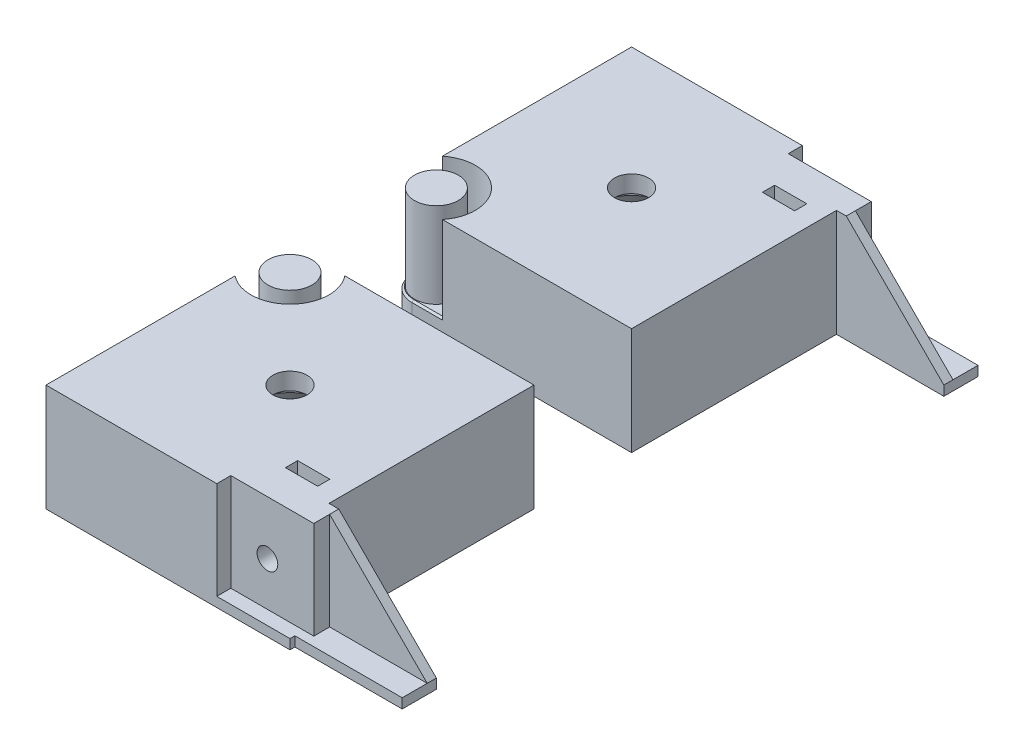
SolidWorks part; units mm, degrees
ref_plane "Front Plane" through (0, 0, 0) normal (0, 0, 1) x (1, 0, 0)
ref_plane "Top Plane" through (0, 0, 0) normal (0, 1, 0) x (1, 0, 0)
ref_plane "Right Plane" through (0, 0, 0) normal (1, 0, 0) x (0, 0, -1)
sketch "Sketch1" plane through (0, 0, 0) normal (0, 1, 0) x (1, 0, 0)
  line L0 (-25, 25) -> (25, -25) construction
  line L1 (-20, 25) -> (25, 25)
  line L2 (-25, 20) -> (-25, -25)
  line L3 (-25, -25) -> (25, -25)
  line L4 (25, 25) -> (25, -25)
  arc A0 (-20, 25) -> (-25, 20) centre (-20, 20) ccw
  point P8 (0, 0)
  dimension "D2" = 5
  dimension "D1" = 50
  dimension "D3" = 45
extrude "Boss-Extrude1" add sketch "Sketch1" along normal blind 11 and the other way blind 11
sketch "Sketch2" plane through (0, 0, 0) normal (0, 0, 1) x (1, 0, 0)
  line L0 (-25, -11) -> (25, -11) construction
  line L1 (-3.5, 7.5) -> (-3.5, 11)
  line L2 (-3.5, 11) -> (0, 11)
  line L3 (-25, 11) -> (25, 11) construction
  line L5 (-18, -11) -> (-10.5, 4)
  line L6 (-10.5, 4) -> (-8, 4)
  line L7 (-8, 4) -> (-8, 7.5)
  line L8 (-8, 7.5) -> (-3.5, 7.5)
  line L9 (0, 11) -> (0, -11)
  line L10 (0, -11) -> (-18, -11)
  line L11 (-8, 4) -> (-8, -11) construction
  line L12 (-10.5, 4) -> (-10.5, -11) construction
  dimension "D1" = 8
  dimension "D2" = 18
  dimension "D3" = 3.5
  dimension "D4" = 2.5
  dimension "D5" = 3.5
  dimension "D6" = 3.5
revolve "Cut-Revolve1" cut sketch "Sketch2" angle 360 about L9
sketch "Sketch3" plane through (25, 0, 0) normal (1, 0, 0) x (0, 0, -1)
  line L0 (-25, 11) -> (25, 11) construction
  line L1 (-24, 11) -> (-22.125, 11)
  line L2 (-24, 11) -> (-24, -11)
  line L3 (-24, -11) -> (-17, -11)
  line L4 (-17, 11) -> (-17, -11)
  line L5 (-25, -11) -> (25, -11) construction
  line L6 (-18.875, 11) -> (-17, 11)
  line L7 (-25, -11) -> (-25, 11) construction
  line L8 (-22.125, 11) -> (-22.125, -9)
  line L9 (-22.125, -9) -> (-18.875, -9)
  line L10 (-18.875, 11) -> (-18.875, -9)
  dimension "D1" = 1
  dimension "D2" = 7
  dimension "D3" = 3.25
  dimension "D4" = 2
extrude "Boss-Extrude2" add sketch "Sketch3" along normal blind 22
sketch "Sketch4" plane through (0, 0, 17) normal (0, 0, -1) x (-1, 0, 0)
  line L0 (-47, -9) -> (-27, 11)
  line L1 (-47, -11) -> (-47, 11) construction
  line L2 (-47, 11) -> (-25, 11) construction
  line L3 (-27, 11) -> (-47, 11)
  line L4 (-47, 11) -> (-47, -9)
  dimension "D1" = 20
extrude "Cut-Extrude1" cut sketch "Sketch4" against normal blind 7
sketch "Sketch5" plane through (0, -9, 0) normal (0, 1, 0) x (1, 0, 0)
  line L1 (25, -18.875) -> (27, -18.875)
  line L2 (25, -18.875) -> (25, -22.125)
  line L3 (25, -22.125) -> (27, -22.125)
  line L4 (27, -18.875) -> (27, -22.125)
extrude "Boss-Extrude3" add sketch "Sketch5" along normal blind 20
sketch "Sketch6" plane through (0, 11, 0) normal (0, 1, 0) x (1, 0, 0)
  line L1 (47, -22.125) -> (10, -22.125)
  line L2 (47, -22.125) -> (47, -25)
  line L3 (47, -25) -> (10, -25)
  line L4 (10, -22.125) -> (10, -25)
  line L5 (-25, -25) -> (25, -25) construction
  line L6 (25, -17) -> (25, 25) construction
  dimension "D1" = 15
extrude "Cut-Extrude2" cut sketch "Sketch6" against normal blind 20
sketch "Sketch8" plane through (0, 0, 22.125) normal (0, 0, 1) x (1, 0, 0)
  line L0 (0, 0) -> (17.5, 0) construction
  line L1 (25, -9) -> (17.5, 0) construction
  line L2 (17.5, 0) -> (10, -9) construction
  line L3 (27, 11) -> (10, 11) construction
  line L4 (14.2, -3.3) -> (20.8, -3.3) construction
  line L5 (14.2, -3.3) -> (14.2, 3.3) construction
  line L6 (14.2, 3.3) -> (20.8, 3.3) construction
  line L7 (20.8, -3.3) -> (20.8, 3.3) construction
  line L8 (14.2, -3.3) -> (20.8, 3.3) construction
  line L9 (14.2, 3.3) -> (20.8, -3.3) construction
  circle A0 centre (17.5, 0) radius 2.125
  dimension "D1" = 4.25
  dimension "D2" = 6.6
  dimension "D3" = 14.3
extrude "Cut-Extrude3" cut sketch "Sketch8" against normal blind 6
sketch "Sketch9" plane through (0, 11, 0) normal (0, 1, 0) x (1, 0, 0)
  line L0 (17.5, -12.625) -> (17.5, -22.125) construction
  line L1 (14.2, -12.625) -> (20.8, -12.625)
  line L2 (14.2, -12.625) -> (14.2, -15.125)
  line L3 (14.2, -15.125) -> (20.8, -15.125)
  line L4 (20.8, -12.625) -> (20.8, -15.125)
  line L7 (15.375, -22.125) -> (19.625, -22.125) construction
  line L8 (15.375, -16.125) -> (19.625, -16.125) construction
  dimension "D1" = 6.6
  dimension "D2" = 2.5
  dimension "D3" = 1
extrude "Cut-Extrude4" cut sketch "Sketch9" against normal blind 14.4
sketch "Sketch11" plane through (0, 0, 16.125) normal (0, 0, 1) x (1, 0, 0)
  circle A0 centre (17.5, 0) radius 2
  dimension "D1" = 4
extrude "Cut-Extrude5" cut sketch "Sketch11" against normal blind 8
sketch "Sketch12" plane through (0, 11, 0) normal (0, 1, 0) x (1, 0, 0)
  circle A0 centre (-20, 20) radius 8
  circle A1 centre (-20, 20) radius 4.5
  dimension "D1" = 16
  dimension "D2" = 9
extrude "Cut-Extrude6" cut sketch "Sketch12" against normal offset from surface (17.5 mm away) 4.5 up to face at (-18, -11, 0)
chamfer "Chamfer1" distance 0.36 angle 45 3 edges at (-16.8775, -6.5, -25) (-23.5355, -6.5, -23.5355) (-25, -6.5, -16.8775)
ref_plane "Plane1" through (0, 0, -35) normal (0, 0, -1) x (-1, 0, 0)
mirror "Mirror2" about plane through (0, 0, -35) normal (0, 0, -1) of bodies 111
